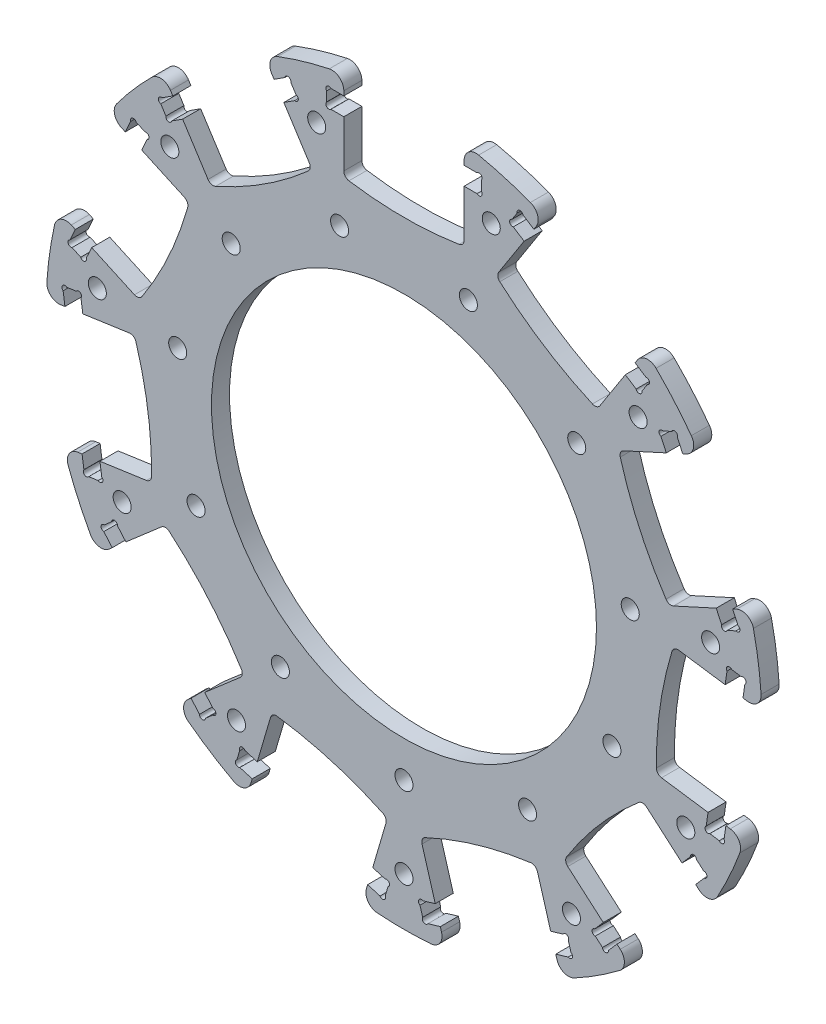
SolidWorks part; units mm, degrees
material "Thornel Mat VMA"
ref_plane "前视基准面" through (0, 0, 0) normal (0, 0, 1) x (1, 0, 0)
ref_plane "上视基准面" through (0, 0, 0) normal (0, 1, 0) x (1, 0, 0)
ref_plane "右视基准面" through (0, 0, 0) normal (1, 0, 0) x (0, 0, -1)
sketch "草图2" plane through (0, 0, 0) normal (0, 0, 1) x (1, 0, 0)
  line L0 (12.85, 52.4) -> (12.85, 55.6) construction
  line L1 (12.85, 55.6) -> (10, 55.6) construction
  line L2 (10, 52.4) -> (12.85, 52.4) construction
  line L3 (9.35, 50.9) -> (10, 50.9) construction
  line L4 (10, 50.9) -> (10, 57.1) construction
  line L5 (10, 57.1) -> (9.35, 57.1) construction
  line L6 (9.35, 46.1078) -> (9.35, 61.8922) construction
  line L7 (8.4948, 45.1184) -> (8.4948, 62.8816) construction
  line L8 (-8.4948, 62.8816) -> (-8.4948, 45.1184) construction
  line L9 (-9.35, 61.8922) -> (-9.35, 46.1078) construction
  line L10 (-10, 50.9) -> (-9.35, 50.9) construction
  line L11 (-9.35, 57.1) -> (-10, 57.1) construction
  line L12 (-10, 57.1) -> (-10, 50.9) construction
  line L13 (-10, 55.6) -> (-12.85, 55.6) construction
  line L14 (-12.85, 52.4) -> (-10, 52.4) construction
  line L15 (-12.85, 55.6) -> (-12.85, 52.4) construction
  line L16 (-8.4948, 54) -> (8.4948, 54) construction
  line L17 (10, 58.6536) -> (10, 43.8392)
  line L18 (-10, 58.6536) -> (-10, 43.8392)
  line L19 (40.1231, 43.9362) -> (32.1138, 31.4735)
  line L20 (23.298, 54.749) -> (15.2887, 42.2863)
  line L21 (57.5074, 15.2693) -> (44.0317, 9.1151)
  line L22 (49.1991, 33.4619) -> (35.7234, 27.3078)
  line L23 (56.6335, -18.2455) -> (41.9698, -16.1372)
  line L24 (59.4798, 1.5509) -> (44.8161, 3.6592)
  line L25 (37.7789, -45.9675) -> (26.5829, -36.2661)
  line L26 (50.8761, -30.8525) -> (39.6801, -21.1511)
  line L27 (6.9297, -59.0951) -> (2.756, -44.8807)
  line L28 (26.1196, -53.4604) -> (21.9459, -39.2461)
  line L29 (-26.1196, -53.4604) -> (-21.9459, -39.2461)
  line L30 (-6.9297, -59.0951) -> (-2.756, -44.8807)
  line L31 (-50.8761, -30.8525) -> (-39.6801, -21.1511)
  line L32 (-37.7789, -45.9675) -> (-26.5829, -36.2661)
  line L33 (-59.4798, 1.5509) -> (-44.8161, 3.6592)
  line L34 (-56.6335, -18.2455) -> (-41.9698, -16.1372)
  line L35 (-49.1991, 33.4619) -> (-35.7234, 27.3078)
  line L36 (-57.5074, 15.2693) -> (-44.0317, 9.1151)
  line L37 (-23.298, 54.749) -> (-15.2887, 42.2863)
  line L38 (-40.1231, 43.9362) -> (-32.1138, 31.4735)
  line L39 (0, 44.5) -> (0, 43) construction
  arc A0 (9.35, 61.8922) -> (8.4948, 62.8816) centre (8.35, 61.8922) ccw construction
  arc A1 (8.4948, 45.1184) -> (9.35, 46.1078) centre (8.35, 46.1078) ccw construction
  arc A2 (-8.4948, 45.1184) -> (8.4948, 45.1184) centre (0, 103.1567) ccw construction
  arc A3 (8.4948, 62.8816) -> (-8.4948, 62.8816) centre (0, 4.8433) ccw construction
  arc A4 (-8.4948, 62.8816) -> (-9.35, 61.8922) centre (-8.35, 61.8922) ccw construction
  arc A5 (-9.35, 46.1078) -> (-8.4948, 45.1184) centre (-8.35, 46.1078) ccw construction
  circle A6 centre (0, 0) radius 59.5 construction
  arc A7 (-10, 43.8392) -> (10, 43.8392) centre (0, 103) ccw
  arc A8 (15.2887, 42.2863) -> (32.1138, 31.4735) centre (55.686, 86.6491) ccw
  arc A9 (35.7234, 27.3078) -> (44.0317, 9.1151) centre (93.6921, 42.7877) ccw
  arc A10 (44.8161, 3.6592) -> (41.9698, -16.1372) centre (101.9516, -14.6584) ccw
  arc A11 (39.6801, -21.1511) -> (26.5829, -36.2661) centre (77.8422, -67.4507) ccw
  arc A12 (21.9459, -39.2461) -> (2.756, -44.8807) centre (29.0185, -98.8278) ccw
  arc A13 (-2.756, -44.8807) -> (-21.9459, -39.2461) centre (-29.0185, -98.8278) ccw
  arc A14 (-26.5829, -36.2661) -> (-39.6801, -21.1511) centre (-77.8422, -67.4507) ccw
  arc A15 (-41.9698, -16.1372) -> (-44.8161, 3.6592) centre (-101.9516, -14.6584) ccw
  arc A16 (-44.0317, 9.1151) -> (-35.7234, 27.3078) centre (-93.6921, 42.7877) ccw
  arc A17 (-32.1138, 31.4735) -> (-15.2887, 42.2863) centre (-55.686, 86.6491) ccw
  arc A18 (-23.298, 54.749) -> (-10, 58.6536) centre (0, 0) cw
  arc A19 (10, 58.6536) -> (23.298, 54.749) centre (0, 0) cw
  arc A20 (40.1231, 43.9362) -> (49.1991, 33.4619) centre (0, 0) cw
  arc A21 (57.5074, 15.2693) -> (59.4798, 1.5509) centre (0, 0) cw
  arc A22 (56.6335, -18.2455) -> (50.8761, -30.8525) centre (0, 0) cw
  arc A23 (37.7789, -45.9675) -> (26.1196, -53.4604) centre (0, 0) cw
  arc A24 (6.9297, -59.0951) -> (-6.9297, -59.0951) centre (0, 0) cw
  arc A25 (-49.1991, 33.4619) -> (-40.1231, 43.9362) centre (0, 0) cw
  arc A26 (-57.5074, 15.2693) -> (-59.4798, 1.5509) centre (0, 0) ccw
  arc A27 (-56.6335, -18.2455) -> (-50.8761, -30.8525) centre (0, 0) ccw
  arc A28 (-37.7789, -45.9675) -> (-26.1196, -53.4604) centre (0, 0) ccw
  circle A29 centre (0, 0) radius 63.5 construction
  circle A30 centre (0, 0) radius 32
  circle A31 centre (0, -51.5) radius 1.5
  circle A32 centre (-27.843, -43.3246) radius 1.5
  circle A33 centre (-46.846, -21.3939) radius 1.5
  circle A34 centre (-50.9758, 7.3292) radius 1.5
  circle A35 centre (-38.9211, 33.7253) radius 1.5
  circle A36 centre (-14.5092, 49.4139) radius 1.5
  circle A37 centre (14.5092, 49.4139) radius 1.5
  circle A38 centre (38.9211, 33.7253) radius 1.5
  circle A39 centre (50.9758, 7.3292) radius 1.5
  circle A40 centre (46.846, -21.3939) radius 1.5
  circle A41 centre (27.843, -43.3246) radius 1.5
  circle A42 centre (0, -38) radius 1.5
  circle A43 centre (-20.5444, -31.9676) radius 1.5
  circle A44 centre (-34.566, -15.7858) radius 1.5
  circle A45 centre (-37.6132, 5.408) radius 1.5
  circle A46 centre (-28.7185, 24.8847) radius 1.5
  circle A47 centre (-10.7058, 36.4607) radius 1.5
  circle A48 centre (10.7058, 36.4607) radius 1.5
  circle A49 centre (28.7185, 24.8847) radius 1.5
  circle A50 centre (37.6132, 5.408) radius 1.5
  circle A51 centre (34.566, -15.7858) radius 1.5
  circle A52 centre (20.5444, -31.9676) radius 1.5
  point P37 (-12.85, 54)
  point P41 (-9.675, 57.1)
  point P42 (-9.675, 50.9)
  point P43 (0, 63.5)
  point P44 (0, 44.5)
  point P45 (-10, 54)
  point P46 (-9.35, 54)
  point P47 (9.35, 54)
  point P48 (10, 54)
  point P49 (12.85, 54)
  point P54 (0, 54)
  point P108 (0, 0)
  point P132 (0, 0)
  point P155 (0, 0)
  dimension "D1" = 25.7
  dimension "D8" = 1
  dimension "D9" = 58.6567
  dimension "D11" = 119
  dimension "D12" = 60
  dimension "D15" = 127
  dimension "D16" = 64
  dimension "D17" = 3
  dimension "D20" = 3
  dimension "D2" = 3.2
  dimension "D3" = 6.2
  dimension "D4" = 20
  dimension "D5" = 19
  dimension "D6" = 18.7
  dimension "D7" = 54
  dimension "D10" = 16.9896
  dimension "D13" = 1.5
  dimension "D18" = 51.5
  dimension "D21" = 38
  dimension "D14" = 11
  dimension "D19" = 11
  dimension "D22" = 11
extrude "凸台-拉伸1" add sketch "草图2" along normal mid plane 3
fillet "圆角1" radius 1 22 edges at (10, 43.8392, 0) (-10, 43.8392, 0) (-15.2887, 42.2863, 0) (-32.1138, 31.4735, 0) (-35.7234, 27.3078, 0) (-44.0317, 9.1151, 0) (-44.8161, 3.6592, 0) (-41.9698, -16.1372, 0) (-39.6801, -21.1511, 0) (-26.5829, -36.2661, 0) (-21.9459, -39.2461, 0) (-2.756, -44.8807, 0) (2.756, -44.8807, 0) (21.9459, -39.2461, 0) (26.5829, -36.2661, 0) (39.6801, -21.1511, 0) (41.9698, -16.1372, 0) (44.8161, 3.6592, 0) (44.0317, 9.1151, 0) (35.7234, 27.3078, 0) (32.1138, 31.4735, 0) (15.2887, 42.2863, 0)
fillet "圆角2" radius 2 22 edges at (10, 58.6536, 0) (-10, 58.6536, 0) (-23.298, 54.749, 0) (-40.1231, 43.9362, 0) (-49.1991, 33.4619, 0) (-57.5074, 15.2693, 0) (-59.4798, 1.5509, 0) (-56.6335, -18.2455, 0) (-50.8761, -30.8525, 0) (-37.7789, -45.9675, 0) (-26.1196, -53.4604, 0) (-6.9297, -59.0951, 0) (6.9297, -59.0951, 0) (26.1196, -53.4604, 0) (37.7789, -45.9675, 0) (50.8761, -30.8525, 0) (56.6335, -18.2455, 0) (59.4798, 1.5509, 0) (57.5074, 15.2693, 0) (49.1991, 33.4619, 0) (40.1231, 43.9362, 0) (23.298, 54.749, 0)
ref_axis "基准轴1" through (0, 0, 1.5) along (0, 0, -1)
sketch "草图3" plane through (0, 0, 1.5) normal (0, 0, 1) x (1, 0, 0)
  line L0 (-10, 54) -> (10, 54) construction
  line L1 (-10, 52.5) -> (-12.85, 52.5)
  line L2 (-10, 44.6905) -> (-10, 56.2339) construction
  line L3 (-12.85, 52.5) -> (-12.85, 55.5)
  line L4 (-12.85, 55.5) -> (-10, 55.5)
  line L5 (-10, 55.5) -> (-10, 52.5)
  line L6 (10, 55.5) -> (12.85, 55.5)
  line L7 (10, 56.2339) -> (10, 44.6905) construction
  line L8 (12.85, 55.5) -> (12.85, 52.5)
  line L9 (12.85, 52.5) -> (10, 52.5)
  line L10 (10, 52.5) -> (10, 55.5)
  line L11 (19.9711, 49.5722) -> (17.5735, 51.113)
  line L12 (17.5735, 51.113) -> (19.1955, 53.6368)
  line L13 (19.1955, 53.6368) -> (21.593, 52.096)
  line L14 (38.4181, 41.2832) -> (40.8157, 39.7423)
  line L15 (40.8157, 39.7423) -> (39.1938, 37.2186)
  line L16 (39.1938, 37.2186) -> (36.7962, 38.7594)
  line L17 (36.7962, 38.7594) -> (38.4181, 41.2832)
  line L18 (21.593, 52.096) -> (19.9711, 49.5722)
  line L19 (43.6015, 30.9056) -> (42.4176, 33.4981)
  line L20 (42.4176, 33.4981) -> (45.1465, 34.7443)
  line L21 (45.1465, 34.7443) -> (46.3304, 32.1519)
  line L22 (54.6387, 13.9592) -> (55.8227, 11.3668)
  line L23 (55.8227, 11.3668) -> (53.0938, 10.1205)
  line L24 (53.0938, 10.1205) -> (51.9098, 12.713)
  line L25 (51.9098, 12.713) -> (54.6387, 13.9592)
  line L26 (46.3304, 32.1519) -> (43.6015, 30.9056)
  line L27 (53.3888, 2.4267) -> (53.7944, 5.2477)
  line L28 (53.7944, 5.2477) -> (56.7638, 4.8207)
  line L29 (56.7638, 4.8207) -> (56.3582, 1.9997)
  line L30 (53.5119, -17.7967) -> (53.1063, -20.6177)
  line L31 (53.1063, -20.6177) -> (50.1369, -20.1907)
  line L32 (50.1369, -20.1907) -> (50.5425, -17.3697)
  line L33 (50.5425, -17.3697) -> (53.5119, -17.7967)
  line L34 (56.3582, 1.9997) -> (53.3888, 2.4267)
  line L35 (46.2255, -26.8227) -> (48.0918, -24.6688)
  line L36 (48.0918, -24.6688) -> (50.3591, -26.6334)
  line L37 (50.3591, -26.6334) -> (48.4927, -28.7873)
  line L38 (35.3955, -43.9023) -> (33.5291, -46.0562)
  line L39 (33.5291, -46.0562) -> (31.2619, -44.0916)
  line L40 (31.2619, -44.0916) -> (33.1282, -41.9377)
  line L41 (33.1282, -41.9377) -> (35.3955, -43.9023)
  line L42 (48.4927, -28.7873) -> (46.2255, -26.8227)
  line L43 (24.3859, -47.5561) -> (27.1204, -46.7531)
  line L44 (27.1204, -46.7531) -> (27.9656, -49.6316)
  line L45 (27.9656, -49.6316) -> (25.2311, -50.4345)
  line L46 (6.0412, -56.0692) -> (3.3067, -56.8721)
  line L47 (3.3067, -56.8721) -> (2.4615, -53.9936)
  line L48 (2.4615, -53.9936) -> (5.196, -53.1907)
  line L49 (5.196, -53.1907) -> (6.0412, -56.0692)
  line L50 (25.2311, -50.4345) -> (24.3859, -47.5561)
  line L51 (-5.196, -53.1907) -> (-2.4615, -53.9936)
  line L52 (-2.4615, -53.9936) -> (-3.3067, -56.8721)
  line L53 (-3.3067, -56.8721) -> (-6.0412, -56.0692)
  line L54 (-25.2311, -50.4345) -> (-27.9656, -49.6316)
  line L55 (-27.9656, -49.6316) -> (-27.1204, -46.7531)
  line L56 (-27.1204, -46.7531) -> (-24.3859, -47.5561)
  line L57 (-24.3859, -47.5561) -> (-25.2311, -50.4345)
  line L58 (-6.0412, -56.0692) -> (-5.196, -53.1907)
  line L59 (-33.1282, -41.9377) -> (-31.2619, -44.0916)
  line L60 (-31.2619, -44.0916) -> (-33.5291, -46.0562)
  line L61 (-33.5291, -46.0562) -> (-35.3955, -43.9023)
  line L62 (-48.4927, -28.7873) -> (-50.3591, -26.6334)
  line L63 (-50.3591, -26.6334) -> (-48.0918, -24.6688)
  line L64 (-48.0918, -24.6688) -> (-46.2255, -26.8227)
  line L65 (-46.2255, -26.8227) -> (-48.4927, -28.7873)
  line L66 (-35.3955, -43.9023) -> (-33.1282, -41.9377)
  line L67 (-50.5425, -17.3697) -> (-50.1369, -20.1907)
  line L68 (-50.1369, -20.1907) -> (-53.1063, -20.6177)
  line L69 (-53.1063, -20.6177) -> (-53.5119, -17.7967)
  line L70 (-56.3582, 1.9997) -> (-56.7638, 4.8207)
  line L71 (-56.7638, 4.8207) -> (-53.7944, 5.2477)
  line L72 (-53.7944, 5.2477) -> (-53.3888, 2.4267)
  line L73 (-53.3888, 2.4267) -> (-56.3582, 1.9997)
  line L74 (-53.5119, -17.7967) -> (-50.5425, -17.3697)
  line L75 (-51.9098, 12.713) -> (-53.0938, 10.1205)
  line L76 (-53.0938, 10.1205) -> (-55.8227, 11.3668)
  line L77 (-55.8227, 11.3668) -> (-54.6387, 13.9592)
  line L78 (-46.3304, 32.1519) -> (-45.1465, 34.7443)
  line L79 (-45.1465, 34.7443) -> (-42.4176, 33.4981)
  line L80 (-42.4176, 33.4981) -> (-43.6015, 30.9056)
  line L81 (-43.6015, 30.9056) -> (-46.3304, 32.1519)
  line L82 (-54.6387, 13.9592) -> (-51.9098, 12.713)
  line L83 (-36.7962, 38.7594) -> (-39.1938, 37.2186)
  line L84 (-39.1938, 37.2186) -> (-40.8157, 39.7423)
  line L85 (-40.8157, 39.7423) -> (-38.4181, 41.2832)
  line L86 (-21.593, 52.096) -> (-19.1955, 53.6368)
  line L87 (-19.1955, 53.6368) -> (-17.5735, 51.113)
  line L88 (-17.5735, 51.113) -> (-19.9711, 49.5722)
  line L89 (-19.9711, 49.5722) -> (-21.593, 52.096)
  line L90 (-38.4181, 41.2832) -> (-36.7962, 38.7594)
  point P2 (0, 54)
  point P17 (-10, 54)
  point P18 (10, 54)
  point P100 (0, 0)
  dimension "D1" = 54
  dimension "D2" = 20
  dimension "D3" = 3
  dimension "D4" = 25.7
  dimension "D5" = 11
extrude "切除-拉伸1" cut sketch "草图3" against normal through all
sketch "草图4" plane through (0, 0, 1.5) normal (0, 0, 1) x (1, 0, 0)
  line L0 (-12.85, 55.5) -> (-11.35, 54) construction
  line L1 (-11.35, 54) -> (-12.85, 52.5) construction
  line L2 (-12.85, 55.5) -> (-12.85, 52.5) construction
  line L3 (-12.85, 52.5) -> (-10, 52.5) construction
  line L4 (12.85, 55.5) -> (11.35, 54) construction
  line L5 (11.35, 54) -> (12.85, 52.5) construction
  line L6 (-10, 55.5) -> (-12.85, 55.5) construction
  line L7 (12.85, 55.5) -> (10, 55.5) construction
  line L9 (10, 52.5) -> (12.85, 52.5) construction
  circle A0 centre (12.4964, 55.1464) radius 0.5
  circle A1 centre (12.4964, 52.8536) radius 0.5
  circle A2 centre (-12.4964, 55.1464) radius 0.5
  circle A3 centre (-12.4964, 52.8536) radius 0.5
  circle A4 centre (19.3017, 53.1482) radius 0.5
  circle A5 centre (18.0621, 51.2193) radius 0.5
  circle A6 centre (40.3271, 39.6361) radius 0.5
  circle A7 centre (39.0875, 37.7071) radius 0.5
  circle A8 centre (44.9718, 34.2758) radius 0.5
  circle A9 centre (42.8861, 33.3233) radius 0.5
  circle A10 centre (55.3542, 11.5415) radius 0.5
  circle A11 centre (53.2685, 10.589) radius 0.5
  circle A12 centre (56.3636, 4.5211) radius 0.5
  circle A13 centre (54.094, 4.8474) radius 0.5
  circle A14 centre (52.8067, -20.2174) radius 0.5
  circle A15 centre (50.5372, -19.8911) radius 0.5
  circle A16 centre (49.8603, -26.6691) radius 0.5
  circle A17 centre (48.1275, -25.1675) radius 0.5
  circle A18 centre (33.4935, -45.5574) radius 0.5
  circle A19 centre (31.7606, -44.0559) radius 0.5
  circle A20 centre (27.5268, -49.392) radius 0.5
  circle A21 centre (26.8808, -47.192) radius 0.5
  circle A22 centre (3.5463, -56.4333) radius 0.5
  circle A23 centre (2.9003, -54.2333) radius 0.5
  circle A24 centre (-3.5463, -56.4333) radius 0.5
  circle A25 centre (-2.9003, -54.2333) radius 0.5
  circle A26 centre (-27.5268, -49.392) radius 0.5
  circle A27 centre (-26.8808, -47.192) radius 0.5
  circle A28 centre (-33.4935, -45.5574) radius 0.5
  circle A29 centre (-31.7606, -44.0559) radius 0.5
  circle A30 centre (-49.8603, -26.6691) radius 0.5
  circle A31 centre (-48.1275, -25.1675) radius 0.5
  circle A32 centre (-52.8067, -20.2174) radius 0.5
  circle A33 centre (-50.5372, -19.8911) radius 0.5
  circle A34 centre (-56.3636, 4.5211) radius 0.5
  circle A35 centre (-54.094, 4.8474) radius 0.5
  circle A36 centre (-55.3542, 11.5415) radius 0.5
  circle A37 centre (-53.2685, 10.589) radius 0.5
  circle A38 centre (-44.9718, 34.2758) radius 0.5
  circle A39 centre (-42.8861, 33.3233) radius 0.5
  circle A40 centre (-40.3271, 39.6361) radius 0.5
  circle A41 centre (-39.0875, 37.7071) radius 0.5
  circle A42 centre (-19.3017, 53.1482) radius 0.5
  circle A43 centre (-18.0621, 51.2193) radius 0.5
  point P110 (0, 0)
  dimension "D5" = 1
  dimension "D1" = 45
  dimension "D2" = 45
  dimension "D3" = 45
  dimension "D4" = 45
  dimension "D6" = 11
extrude "切除-拉伸2" cut sketch "草图4" against normal through all
